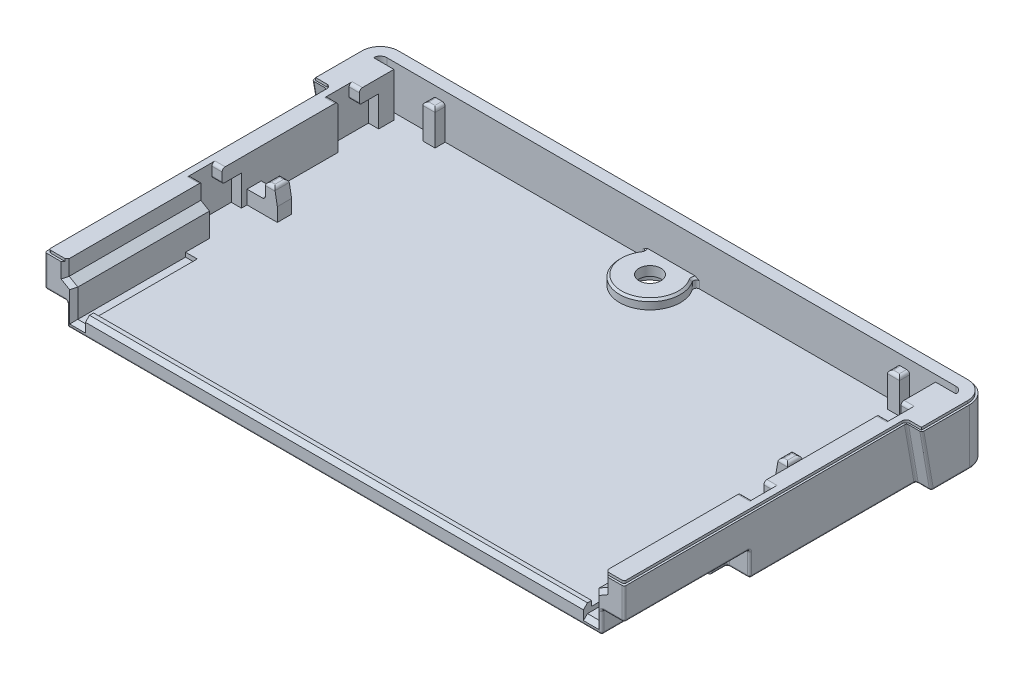
SolidWorks part; units mm, degrees
ref_plane "Front Plane" through (0, 0, 0) normal (0, 0, 1) x (1, 0, 0)
ref_plane "Top Plane" through (0, 0, 0) normal (0, 1, 0) x (1, 0, 0)
ref_plane "Right Plane" through (0, 0, 0) normal (1, 0, 0) x (0, 0, -1)
sketch "Sketch1" plane through (0, 0, 0) normal (0, 1, 0) x (1, 0, 0)
  line L1 (28, 1.35) -> (0, 1.35)
  line L2 (30, -0.65) -> (30, -5.4)
  line L3 (28.5, -19.8) -> (26.65, -19.8)
  line L5 (26.65, -17.55) -> (26.65, -6.15)
  line L6 (28, 0) -> (23.453, 0)
  line L11 (0, 1.35) -> (0, 0)
  line L14 (30, -5.4) -> (28.5, -5.4)
  line L15 (28.5, -19.8) -> (28.5, -5.4)
  line L16 (26.65, -19.8) -> (26.65, -5.4) construction
  line L17 (26.65, -0.65) -> (28.65, -0.65)
  line L18 (22.253, 0) -> (0, 0)
  line L20 (22.253, 0) -> (22.253, -1)
  line L21 (22.253, -1) -> (23.453, -1)
  line L22 (23.453, 0) -> (23.453, -1)
  line L23 (28, 0) -> (0, 0) construction
  line L24 (26.65, -4.05) -> (26.65, -0.65)
  line L27 (26.65, -17.55) -> (27.65, -17.55)
  line L28 (27.65, -19.65) -> (27.65, -17.55)
  line L29 (26.65, -4.05) -> (27.65, -4.05)
  line L31 (26.65, -6.15) -> (27.65, -6.15)
  line L32 (27.65, -4.05) -> (27.65, -6.15)
  line L33 (0, 1.35) -> (0, -19.8) construction
  line L36 (27.65, -19.65) -> (26.65, -19.65)
  line L37 (26.65, -19.8) -> (26.65, -19.65)
  arc A0 (30, -0.65) -> (28, 1.35) centre (28, -0.65) ccw
  arc A1 (28.65, -0.65) -> (28, 0) centre (28, -0.65) ccw
  point P0 (0, 0)
  dimension "D4" = 2
  dimension "D1" = 21.15
  dimension "D2" = 60
  dimension "D3" = 57
  dimension "D5" = 6.75
  dimension "D8" = 1.2
  dimension "D9" = 7.747
  dimension "D10" = 1
  dimension "D11" = 2.1
  dimension "D12" = 1
  dimension "D13" = 15.6
  dimension "D14" = 2.1
  dimension "D15" = 1
  dimension "D16" = 0.15
  dimension "D6" = 53.3
  dimension "D7" = 1.35
extrude "Boss-Extrude1" add sketch "Sketch1" along normal blind 5.75
sketch "Sketch12" plane through (0, 0, 19.8) normal (0, 0, 1) x (1, 0, 0)
  line L0 (26.5, 4.2407) -> (26.5, 5.75)
  line L1 (28.5, 5.75) -> (28.5, 2.4)
  line L2 (0, 0) -> (0, 10.6784) construction
  line L3 (28.5, 2.4) -> (26.3, 2.4)
  line L4 (26.3, 2.4) -> (26.3, 0)
  line L5 (23.453, 0) -> (28, 0) construction
  line L6 (26.3, 0) -> (0, 0)
  line L7 (0, 0) -> (0, 1.42)
  line L8 (0, 5.75) -> (0, 0) construction
  line L9 (0, 1.42) -> (25.65, 1.42)
  line L10 (25.65, 1.42) -> (25.65, 3.75)
  line L12 (28.5, 5.75) -> (30, 5.75) construction
  line L13 (26.5, 5.75) -> (28.5, 5.75)
  line L14 (28.5, 5.75) -> (28.5, 0) construction
  line L15 (26.5, 4.2407) -> (25.65, 3.75)
  dimension "D1" = 3.35
  dimension "D2" = 53
  dimension "D3" = 1.42
  dimension "D4" = 60
  dimension "D5" = 2.33
  dimension "D6" = 2.2
  dimension "D7" = 51.3
extrude "Boss-Extrude4" add sketch "Sketch12" along normal blind 13.35
sketch "Sketch25" plane through (0, 0, 19.8) normal (0, 0, 1) x (1, 0, 0)
  line L0 (26.3, 0) -> (26.3, 2.4) construction
  line L1 (26.3, 2.4) -> (26.3, 0)
  line L2 (26.65, 0) -> (28.5, 0) construction
  line L3 (28.5, 2.4) -> (28.5, 0) construction
  line L4 (26.65, 2.4) -> (28.5, 2.4) construction
  line L8 (28.5, 2.4) -> (26.3, 2.4)
  line L10 (26.3, 0) -> (28.5, 0)
  line L11 (28.5, 0) -> (28.5, 2.4)
extrude "Boss-Extrude7" add sketch "Sketch25" along normal blind 1
sketch "Sketch13" plane through (0, 0, 0) normal (0, -1, 0) x (1, 0, 0)
  line L0 (0, 33.15) -> (0, 19.8) construction
  line L1 (26.3, 20.8) -> (28.5, 20.8) construction
  line L2 (28, -1.35) -> (0, -1.35) construction
  line L3 (30, 5.4) -> (30, 0.65) construction
  line L4 (28.5, 5.4) -> (30, 5.4) construction
  line L5 (28.5, 20.8) -> (28.5, 5.4) construction
  line L6 (26.3, 20.8) -> (28.5, 20.8)
  line L8 (0, 33.15) -> (26.3, 33.15) construction
  line L9 (0, 33.15) -> (0, -1.35)
  line L10 (26.3, 33.15) -> (26.3, 20.8)
  line L11 (28, -1.35) -> (0, -1.35)
  line L12 (30, 5.4) -> (30, 0.65)
  line L13 (28.5, 5.4) -> (30, 5.4)
  line L14 (28.5, 20.8) -> (28.5, 5.4)
  line L17 (0, 33.15) -> (26.3, 33.15)
  arc A0 (28, -1.35) -> (30, 0.65) centre (28, 0.65) ccw construction
  arc A1 (28, -1.35) -> (30, 0.65) centre (28, 0.65) ccw
extrude "Boss-Extrude5" add sketch "Sketch13" against normal up to surface (1.42 mm away) up to face at (12.825, 1.42, 26.475)
sketch "Sketch15" plane through (0, 0, 33.15) normal (0, 0, 1) x (1, 0, 0)
  line L0 (0, 0) -> (26.3, 0) construction
  line L1 (25.65, 1.42) -> (24.5, 1.42)
  line L2 (25.65, 1.42) -> (25.65, 1)
  line L3 (25.65, 1) -> (24.5, 1)
  line L4 (24.5, 1.42) -> (24.5, 1)
  dimension "D1" = 1
  dimension "D2" = 1.15
extrude "Cut-Extrude9" cut sketch "Sketch15" against normal blind 11
sketch "Sketch16" plane through (26.65, 0, 0) normal (-1, 0, 0) x (0, 0, 1)
  line L0 (17.55, 5.75) -> (17.55, 1.42) construction
  line L1 (17.55, 4.42) -> (15.65, 4.42)
  line L2 (17.55, 4.42) -> (17.55, 1.42)
  line L3 (17.55, 1.42) -> (15.65, 1.42)
  line L4 (15.65, 4.42) -> (15.65, 1.42)
  line L5 (17.55, 1.42) -> (6.15, 1.42) construction
  line L6 (19.65, 5.75) -> (19.65, 1.42) construction
  line L8 (4.05, 1.42) -> (2.15, 1.42)
  line L9 (4.05, 1.42) -> (4.05, 4.42)
  line L10 (4.05, 4.42) -> (2.15, 4.42)
  line L11 (2.15, 1.42) -> (2.15, 4.42)
  dimension "D1" = 4
  dimension "D2" = 3
extrude "Cut-Extrude10" cut sketch "Sketch16" against normal up to surface (1 mm away) up to face at (27.65, 3.585, 5.1)
sketch "Sketch19" plane through (0, 5.75, 0) normal (0, 1, 0) x (1, 0, 0)
  line L1 (22.253, -1) -> (23.453, -1)
  line L2 (22.253, -1) -> (22.253, 0)
  line L3 (22.253, 0) -> (23.453, 0)
  line L4 (23.453, -1) -> (23.453, 0)
extrude "Cut-Extrude13" cut sketch "Sketch19" against normal blind 1
sketch "Sketch22" plane through (0, 0, 0) normal (0, -1, 0) x (1, 0, 0)
  line L0 (0, -1.35) -> (0, 33.15) construction
  line L1 (26.3, 33.15) -> (0, 33.15)
  line L2 (26.3, 33.15) -> (26.3, 22.4)
  line L3 (26.3, 22.4) -> (0, 22.4)
  line L4 (0, 33.15) -> (0, 22.4)
  dimension "D1" = 10.75
extrude "Cut-Extrude16" cut sketch "Sketch22" against normal blind 0.25
sketch "Sketch23" plane through (0, 0, 0) normal (0, -1, 0) x (1, 0, 0)
  line L0 (28, -1.35) -> (0, -1.35) construction
  line L1 (13.9, -1.35) -> (16.9, -1.35)
  line L2 (13.9, -1.35) -> (13.9, 22.4)
  line L3 (13.9, 22.4) -> (16.9, 22.4)
  line L4 (16.9, -1.35) -> (16.9, 22.4)
  line L5 (0, 22.4) -> (26.3, 22.4) construction
  line L6 (28.5, 20.8) -> (28.5, 5.4) construction
  dimension "D1" = 3
  dimension "D2" = 11.6
extrude "Cut-Extrude17" cut sketch "Sketch23" against normal blind 0.1
sketch "Sketch31" plane through (30, 0, 0) normal (1, 0, 0) x (0, 0, -1)
  line L0 (-5.4, 5.75) -> (-5.4, 0)
  line L1 (-5.4, 0) -> (-4.4, 0)
  line L2 (-4.4, 0) -> (-5.4, 5.75)
  dimension "D1" = 1
extrude "Cut-Extrude19" cut sketch "Sketch31" against normal up to surface (1.5 mm away) up to face at (28.5, 2.7167, 19.7833)
fillet "Fillet1" radius 0.2 2 edges at (27.15, 4.42, 17.55) (27.15, 4.42, 4.05)
fillet "Fillet2" radius 0.2 20 edges at (30, 0, 2.525) (29.4142, 0, -0.7642) (26.3, 0, 21.6) (26.3, 0.125, 22.4) (26.3, 2.4, 26.975) (28.5, 4.075, 33.15) (27.4, 2.4, 33.15) (26.3, 1.325, 33.15) (13.15, 0.25, 33.15) (26.3, 0.25, 27.775) (28.5, 2.4, 26.975) (28.5, 0, 12.6) (22.45, 0, -1.35) (27.4, 2.4, 20.8) (26.3, 1.2, 20.8) (27.4, 0, 20.8) (28.5, 1.2, 20.8) (29.25, 0, 4.4) (30, 2.875, 4.9) (28.5, 2.875, 4.9)
mirror "Mirror1" about plane through (0, 0, 0) normal (1, 0, 0) of "Cut-Extrude19", "Boss-Extrude1", "Boss-Extrude7", "Boss-Extrude4", "Boss-Extrude5", "Cut-Extrude10", "Cut-Extrude9", "Cut-Extrude13", "Cut-Extrude17", "Fillet1", "Cut-Extrude16", "Fillet2"
sketch "Sketch18" plane through (0, 1.42, 0) normal (0, 1, 0) x (1, 0, 0)
  line L0 (0, 0) -> (0, -33.15) construction
  line L2 (24.5, -33.15) -> (-24.5, -33.15) construction
  line L3 (22.253, 0) -> (-22.253, 0) construction
  line L4 (-28, 0) -> (28, 0) construction
  circle A0 centre (0, -2.1) radius 3
  dimension "D1" = 6
  dimension "D2" = 5.1
extrude "Boss-Extrude6" add sketch "Sketch18" along normal blind 0.9
sketch "Sketch17" plane through (0, 1.42, 0) normal (0, 1, 0) x (1, 0, 0)
  line L0 (0, 0) -> (0, -33.15) construction
  line L1 (24.5, -33.15) -> (-24.5, -33.15) construction
  circle A0 centre (0, -2.1) radius 1.075
  arc A2 (-2.1424, 0) -> (2.1424, 0) centre (0, -2.1) ccw construction
  dimension "D1" = 2.15
extrude "Cut-Extrude12" cut sketch "Sketch17" against normal through all both and the other way through all
sketch "Sketch20" plane through (0, 0, 0) normal (0, -1, 0) x (1, 0, 0)
  circle A0 centre (0, 2.1) radius 2.6
  dimension "D1" = 5.2
extrude "Cut-Extrude14" cut sketch "Sketch20" against normal blind 1.4
sketch "Sketch24" plane through (0, 5.75, 0) normal (0, 1, 0) x (1, 0, 0)
  line L5 (28.3, -33.15) -> (26.5, -33.15) construction
  line L6 (28.5, -32.95) -> (28.5, -5.603) construction
  line L8 (28.7, -5.4) -> (29.8, -5.4) construction
  line L30 (30, -5.197) -> (30, -0.65) construction
  line L31 (28, 1.35) -> (-28, 1.35) construction
  line L32 (-30, -5.197) -> (-30, -0.65) construction
  line L33 (-28.7, -5.4) -> (-29.8, -5.4) construction
  line L34 (-28.5, -32.95) -> (-28.5, -5.603) construction
  line L35 (-28.3, -33.15) -> (-26.5, -33.15) construction
  line L78 (28.3, -33.15) -> (26.5, -33.15)
  line L79 (28.5, -32.95) -> (28.5, -5.603)
  line L80 (28.7, -5.4) -> (29.8, -5.4)
  line L81 (30, -5.197) -> (30, -0.65)
  line L82 (28, 1.35) -> (-28, 1.35)
  line L83 (-30, -5.197) -> (-30, -0.65)
  line L84 (-28.7, -5.4) -> (-29.8, -5.4)
  line L85 (-28.5, -32.95) -> (-28.5, -5.603)
  line L86 (-28.3, -33.15) -> (-26.5, -33.15)
  line L87 (-28.3, -32.95) -> (-26.5, -32.95)
  line L88 (-28.3, -32.95) -> (-28.3, -5.603)
  line L89 (-28.7, -5.2) -> (-29.7991, -5.2)
  line L90 (-29.8, -5.197) -> (-29.8, -0.65)
  line L91 (28, 1.15) -> (-28, 1.15)
  line L92 (29.8, -5.197) -> (29.8, -0.65)
  line L93 (28.7, -5.2) -> (29.7991, -5.2)
  line L94 (28.3, -32.95) -> (28.3, -5.603)
  line L95 (28.3, -32.95) -> (26.5, -32.95)
  line L96 (-26.5, -32.95) -> (-26.5, -33.15)
  line L97 (26.5, -32.95) -> (26.5, -33.15)
  arc A18 (28.3, -33.15) -> (28.5, -32.95) centre (28.3, -32.95) ccw construction
  arc A19 (30, -0.65) -> (28, 1.35) centre (28, -0.65) ccw construction
  arc A20 (-28, 1.35) -> (-30, -0.65) centre (-28, -0.65) ccw construction
  arc A21 (-28.5, -32.95) -> (-28.3, -33.15) centre (-28.3, -32.95) ccw construction
  arc A23 (28.3, -33.15) -> (28.5, -32.95) centre (28.3, -32.95) ccw
  arc A24 (30, -0.65) -> (28, 1.35) centre (28, -0.65) ccw
  arc A25 (-28, 1.35) -> (-30, -0.65) centre (-28, -0.65) ccw
  arc A26 (-28.5, -32.95) -> (-28.3, -33.15) centre (-28.3, -32.95) ccw
  arc A59 (-28.3, -32.95) -> (-28.3, -32.95) centre (-28.3, -32.95) ccw
  arc A60 (-28, 1.15) -> (-29.8, -0.65) centre (-28, -0.65) ccw
  arc A61 (29.8, -0.65) -> (28, 1.15) centre (28, -0.65) ccw
  arc A62 (28.3, -32.95) -> (28.3, -32.95) centre (28.3, -32.95) ccw
  ellipse E0 centre (28.7, -5.603) end of major axis (28.7, -5.4) minor radius 0.2 (28.7, -5.4) -> (28.5, -5.603) ccw construction
  ellipse E1 centre (29.8, -5.197) end of major axis (29.8, -5.4) minor radius 0.2 (29.8, -5.4) -> (30, -5.197) ccw construction
  ellipse E2 centre (-29.8, -5.197) end of major axis (-29.8, -5.4) minor radius 0.2 (-30, -5.197) -> (-29.8, -5.4) ccw construction
  ellipse E3 centre (-28.7, -5.603) end of major axis (-28.7, -5.4) minor radius 0.2 (-28.5, -5.603) -> (-28.7, -5.4) ccw construction
  ellipse E4 centre (28.7, -5.603) end of major axis (28.7, -5.4) minor radius 0.2 (28.7, -5.4) -> (28.5, -5.603) ccw
  ellipse E5 centre (29.8, -5.197) end of major axis (29.8, -5.4) minor radius 0.2 (29.8, -5.4) -> (30, -5.197) ccw
  ellipse E6 centre (-29.8, -5.197) end of major axis (-29.8, -5.4) minor radius 0.2 (-30, -5.197) -> (-29.8, -5.4) ccw
  ellipse E7 centre (-28.7, -5.603) end of major axis (-28.7, -5.4) minor radius 0.2 (-28.5, -5.603) -> (-28.7, -5.4) ccw
  spline S0 degree 1 poles (-28.3, -5.603) (-28.7, -5.2) knots 0 0 1 1 construction
  spline S1 degree 1 poles (-29.8, -5.197) (-29.7991, -5.2) knots 0 0 1 1 construction
  spline S2 degree 1 poles (29.7991, -5.2) (29.8, -5.197) knots 0 0 1 1 construction
  spline S3 degree 1 poles (28.7, -5.2) (28.3, -5.603) knots 0 0 1 1 construction
  spline S4 degree 3 poles (-28.3, -5.603) (-28.3, -5.5509) (-28.3205, -5.4458) (-28.4086, -5.3119) (-28.5416, -5.2213) (-28.6476, -5.2) (-28.7, -5.2) knots -1.570796 -1.570796 -1.570796 -1.570796 -1.178097 -0.785398 -0.392699 0 0 0 0
  spline S5 degree 3 poles (-29.7991, -5.2) (-29.7992, -5.1999) (-29.7994, -5.1996) (-29.7997, -5.1989) (-29.7999, -5.198) (-29.8, -5.1973) (-29.8, -5.197) knots -1.570796 -1.570796 -1.570796 -1.570796 -1.403331 -1.235866 -1.068401 -0.900935 -0.900935 -0.900935 -0.900935
  spline S6 degree 3 poles (29.8, -5.197) (29.8, -5.1973) (29.7999, -5.198) (29.7997, -5.1989) (29.7994, -5.1996) (29.7992, -5.1999) (29.7991, -5.2) knots 0.900935 0.900935 0.900935 0.900935 1.068401 1.235866 1.403331 1.570796 1.570796 1.570796 1.570796
  spline S7 degree 3 poles (28.7, -5.2) (28.6476, -5.2) (28.5416, -5.2213) (28.4086, -5.3119) (28.3205, -5.4458) (28.3, -5.5509) (28.3, -5.603) knots 0 0 0 0 0.392699 0.785398 1.178097 1.570796 1.570796 1.570796 1.570796
  dimension "D1" = 0.2
extrude "Cut-Extrude18" cut sketch "Sketch24" against normal blind 0.25
fillet "Fillet4" radius 0.3 2 edges at (-2.1424, 1.87, 0) (2.1424, 1.87, 0)
chamfer "Chamfer1" distance 0.2 angle 45 3 edges at (0, 2.32, 5.1) (-2.5021, 2.32, 0.157) (2.5021, 2.32, 0.157)
sketch "Sketch27" plane through (0, 0, 0) normal (0, 0, 1) x (1, 0, 0)
  line L1 (26.65, 1.42) -> (23.67, 1.42)
  line L2 (26.65, 1.42) -> (26.65, 2.77)
  line L3 (26.65, 2.77) -> (24.85, 2.77)
  line L4 (23.67, 1.42) -> (23.67, 2.77)
  line L6 (24.85, 2.77) -> (24.85, 4.27)
  line L7 (24.85, 4.27) -> (23.9345, 4.27)
  line L8 (23.9345, 4.27) -> (23.67, 2.77)
  line L9 (28.5, 0.2) -> (28.5, 5.5) construction
  dimension "D1" = 4.83
  dimension "D2" = 2.85
  dimension "D3" = 10
  dimension "D4" = 1.5
  dimension "D5" = 1.8
extrude "Boss-Extrude8" add sketch "Sketch27" along normal blind 1.4 from offset 12
sketch "Sketch28" plane through (0, 0, 0) normal (0, 0, 1) x (1, 0, 0)
  line L1 (-26.65, 1.42) -> (-23.67, 1.42)
  line L2 (-26.65, 1.42) -> (-26.65, 2.77)
  line L3 (-26.65, 2.77) -> (-24.85, 2.77)
  line L4 (-23.67, 1.42) -> (-23.67, 2.77)
  line L7 (-23.9345, 4.27) -> (-24.85, 4.27)
  line L8 (-24.85, 2.77) -> (-24.85, 4.27)
  line L9 (-23.9345, 4.27) -> (-23.67, 2.77)
  line L10 (-28.5, 5.5) -> (-28.5, 0.2) construction
  dimension "D1" = 4.83
  dimension "D2" = 1.8
  dimension "D3" = 2.85
  dimension "D4" = 1.5
  dimension "D5" = 10
extrude "Boss-Extrude9" add sketch "Sketch28" along normal blind 1.4 from offset 13.7
fillet "Fillet3" radius 0.3 26 edges at (22.253, 4.75, 0.5) (23.453, 4.75, 0.5) (22.853, 4.75, 1) (-27.15, 5.75, 17.55) (-27.15, 5.75, 6.15) (-27.15, 5.75, 4.05) (-27.15, 5.75, 19.65) (-26.575, 5.75, 19.8) (-22.253, 4.75, 0.5) (-22.853, 4.75, 1) (-23.453, 4.75, 0.5) (26.575, 5.75, 19.8) (27.15, 5.75, 4.05) (27.15, 5.75, 6.15) (27.15, 5.75, 19.65) (27.15, 5.75, 17.55) (24.85, 2.77, 12.7) (24.3922, 4.27, 12) (24.85, 4.27, 12.7) (23.9345, 4.27, 12.7) (24.3922, 4.27, 13.4) (-24.3922, 4.27, 13.7) (-23.9345, 4.27, 14.4) (-24.85, 4.27, 14.4) (-24.85, 2.77, 14.4) (-24.3922, 4.27, 15.1)
sketch "Sketch29" plane through (0, 1.42, 0) normal (0, 1, 0) x (1, 0, 0)
  line L0 (24.5, -33.15) -> (-24.5, -33.15) construction
  line L1 (-24.5, -32.35) -> (24.5, -32.35)
  line L2 (-24.5, -32.35) -> (-24.5, -33.15)
  line L3 (-24.5, -33.15) -> (24.5, -33.15)
  line L4 (24.5, -32.35) -> (24.5, -33.15)
  line L5 (0, 0) -> (0, -37.1086) construction
  line L7 (-24.5, -22.15) -> (-24.5, -33.15) construction
  point P9 (0, -32.35)
  dimension "D1" = 0.8
extrude "Boss-Extrude10" add sketch "Sketch29" along normal blind 0.5
chamfer "Chamfer2" distance 0.4 angle 45 10 edges at (26.5, 4.8704, 33.15) (26.5, 5.625, 32.95) (25.65, 2.375, 33.15) (25.075, 1, 33.15) (-26.5, 4.8704, 33.15) (-25.65, 2.375, 33.15) (-25.075, 1, 33.15) (0, 1.92, 33.15) (26.075, 3.9954, 33.15) (-26.075, 3.9954, 33.15)
sketch "Sketch30" plane through (0, 0, 0) normal (0, 1, 0) x (1, 0, 0)
  line L0 (28, 1.35) -> (-28, 1.35) construction
  line L1 (24.5, -33.15) -> (-24.5, -33.15) construction
  line L2 (24.5, -33.15) -> (-24.5, -33.15)
  line L3 (28, 1.35) -> (-28, 1.35)
  dimension "D1" = 34.5
fillet "Fillet5" radius 0.2 2 edges at (28.3, 5.625, 32.95) (-28.3, 5.625, 32.95)
